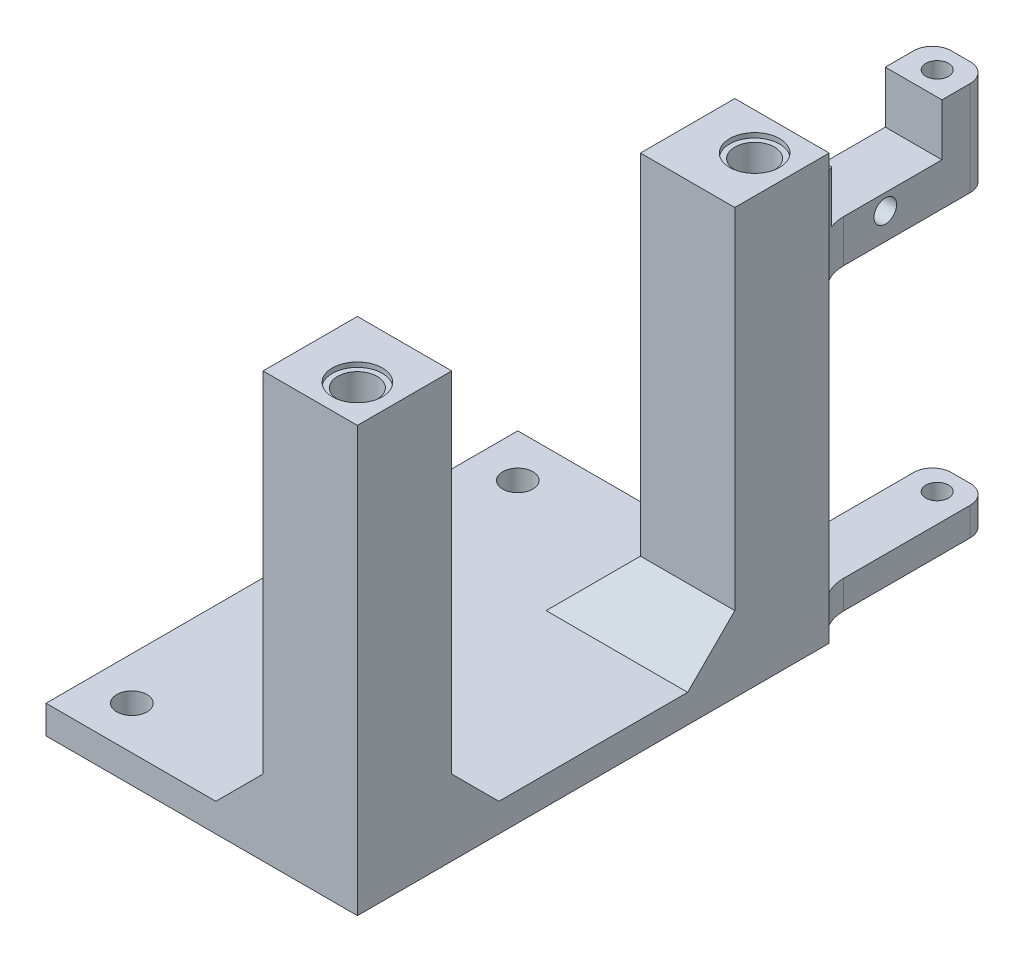
SolidWorks part; units mm, degrees
ref_plane "Front Plane" through (0, 0, 0) normal (0, 0, 1) x (1, 0, 0)
ref_plane "Top Plane" through (0, 0, 0) normal (0, 1, 0) x (1, 0, 0)
ref_plane "Right Plane" through (0, 0, 0) normal (1, 0, 0) x (0, 0, -1)
sketch "Sketch1" plane through (0, 0, 0) normal (0, 1, 0) x (1, 0, 0)
  line L1 (-6.5124, 9.686) -> (1.4876, 9.686)
  line L2 (-6.5124, 9.686) -> (-6.5124, -40.314)
  line L3 (-6.5124, -40.314) -> (1.4876, -40.314)
  line L4 (1.4876, 9.686) -> (1.4876, -40.314)
  line L5 (1.4876, 9.686) -> (26.4876, 9.686)
  line L6 (1.4876, 9.686) -> (1.4876, -40.314)
  line L7 (1.4876, -40.314) -> (26.4876, -40.314)
  line L8 (26.4876, 9.686) -> (26.4876, -40.314)
  circle A0 centre (-1.9624, -35.764) radius 1.6
  circle A1 centre (-1.9624, 5.136) radius 1.6
  dimension "D4" = 3.2
  dimension "D5" = 3.2
  dimension "D6" = 4.55
  dimension "D7" = 4.55
  dimension "D8" = 4.55
  dimension "D9" = 4.55
  dimension "D1" = 8
  dimension "D2" = 50
  dimension "D3" = 25
extrude "Boss-Extrude1" add sketch "Sketch1" along normal blind 3 contours A1 | A0 | L5 L8 L7 L3 L2 L1
sketch "Sketch2" plane through (0, 3, 0) normal (0, 1, 0) x (1, 0, 0)
  line L1 (26.4876, -40.314) -> (16.4876, -40.314)
  line L2 (26.4876, -40.314) -> (26.4876, -30.314)
  line L3 (26.4876, -30.314) -> (16.4876, -30.314)
  line L4 (16.4876, -40.314) -> (16.4876, -30.314)
  line L5 (26.4876, 9.686) -> (16.4876, 9.686)
  line L6 (26.4876, 9.686) -> (26.4876, -0.314)
  line L7 (26.4876, -0.314) -> (16.4876, -0.314)
  line L8 (16.4876, 9.686) -> (16.4876, -0.314)
  dimension "D1" = 10
  dimension "D2" = 10
  dimension "D3" = 10
  dimension "D4" = 10
extrude "Boss-Extrude2" add sketch "Sketch2" along normal blind 42
chamfer "Chamfer1" distance 5 angle 45 4 edges at (16.4876, 3, -4.686) (21.4876, 3, 0.314) (16.4876, 3, 35.314) (21.4876, 3, 30.314)
ref_plane "Plane1" through (0, 45, 0) normal (0, 1, 0) x (1, 0, 0)
sketch "Sketch3" plane through (0, 45, 0) normal (0, 1, 0) x (1, 0, 0)
  line L0 (26.4876, -40.314) -> (26.4876, -30.314) construction
  line L1 (16.4876, -40.314) -> (26.4876, -40.314) construction
  line L2 (26.4876, -0.314) -> (26.4876, 9.686) construction
  line L3 (26.4876, 9.686) -> (16.4876, 9.686) construction
  circle A0 centre (22.5376, -36.364) radius 2.1
  circle A1 centre (22.5376, 5.736) radius 2.1
  dimension "D1" = 4.2
  dimension "D3" = 3.95
  dimension "D4" = 4.2
  dimension "D6" = 3.95
  dimension "D2" = 3.95
  dimension "D5" = 3.95
extrude "Cut-Extrude1" cut sketch "Sketch3" against normal blind 52
sketch "Sketch4" plane through (0, 45, 0) normal (0, 1, 0) x (1, 0, 0)
  circle A0 centre (22.5376, -36.364) radius 2.65
  circle A1 centre (22.5376, 5.736) radius 2.65
  dimension "D1" = 5.3
  dimension "D2" = 5.3
extrude "Cut-Extrude2" cut sketch "Sketch4" against normal blind 0.5
ref_plane "Plane2" through (0, 22.5, 0) normal (0, -1, 0) x (-1, 0, 0)
mirror "Mirror1" about plane through (0, 22.5, 0) normal (0, -1, 0) of "Cut-Extrude2"
sketch "Sketch5" plane through (0, 0, -9.686) normal (0, 0, -1) x (-1, 0, 0)
  line L0 (-22.4876, 36.5) -> (-17.9876, 36.5) construction
  line L1 (-18.2876, 36.2) -> (-24.2876, 36.2)
  line L2 (-18.2876, 36.2) -> (-18.2876, 31.6868)
  line L3 (-18.2876, 31.6868) -> (-24.2876, 31.6868)
  line L4 (-24.2876, 36.2) -> (-24.2876, 31.6868)
  line L5 (-17.9876, 32.25) -> (-17.9876, 37) construction
  dimension "D1" = 0.3
  dimension "D2" = 0.3
  dimension "D3" = 6
extrude "Boss-Extrude3" add sketch "Sketch5" along normal up to surface (14.15 mm away)
sketch "Sketch6" plane through (24.2876, 0, 0) normal (1, 0, 0) x (0, 0, -1)
  circle A0 centre (17.836, 34.5) radius 1.2
  dimension "D1" = 2.4
extrude "Cut-Extrude3" cut sketch "Sketch6" against normal up to surface (6 mm away) up to face at (18.2876, 33.9434, -16.761)
sketch "Sketch7" plane through (0, 0, -23.836) normal (0, 0, -1) x (-1, 0, 0)
  line L1 (-24.2876, 31.6868) -> (-18.2876, 31.6868)
  line L2 (-24.2876, 31.6868) -> (-24.2876, 41.7057)
  line L3 (-24.2876, 41.7057) -> (-18.2876, 41.7057)
  line L4 (-18.2876, 31.6868) -> (-18.2876, 41.7057)
extrude "Boss-Extrude4" add sketch "Sketch7" along normal blind 5
sketch "Sketch8" plane through (0, 0, -9.686) normal (0, 0, -1) x (-1, 0, 0)
  line L0 (-18.2876, 41.7057) -> (-24.2876, 41.7057) construction
  line L1 (-24.2876, 36.2) -> (-18.2687, 36.2)
  line L2 (-24.2876, 36.2) -> (-24.2876, 41.7057)
  line L3 (-24.2876, 41.7057) -> (-18.2687, 41.7057)
  line L4 (-18.2687, 36.2) -> (-18.2687, 41.7057)
extrude "Boss-Extrude5" add sketch "Sketch8" along normal up to surface (2.15 mm away)
sketch "Sketch9" plane through (0, 0, -9.686) normal (0, 0, -1) x (-1, 0, 0)
  line L0 (6.5124, 0) -> (-26.4876, 0) construction
  line L1 (-24.2876, 0) -> (-18.2876, 0)
  line L2 (-24.2876, 0) -> (-24.2876, 3)
  line L3 (-24.2876, 3) -> (-18.2876, 3)
  line L4 (-18.2876, 0) -> (-18.2876, 3)
  line L5 (6.5124, 3) -> (-11.4876, 3) construction
  line L6 (-24.2876, 41.7057) -> (-24.2876, 31.6868) construction
  line L7 (-18.2876, 31.6868) -> (-18.2876, 41.7057) construction
extrude "Boss-Extrude6" add sketch "Sketch9" along normal up to surface (19.15 mm away) up to face at (21.2876, 36.6962, -28.836)
sketch "Sketch10" plane through (0, 41.7057, 0) normal (0, 1, 0) x (1, 0, 0)
  line L0 (18.2876, 23.836) -> (24.2876, 28.836) construction
  line L1 (18.2876, 28.836) -> (24.2876, 23.836) construction
  circle A0 centre (21.2876, 26.336) radius 1.2
  dimension "D1" = 2.4
extrude "Cut-Extrude4" cut sketch "Sketch10" against normal through all
fillet "Fillet3" radius 2 4 edges at (18.2876, 1.5, -28.836) (24.2876, 1.5, -28.836) (18.2876, 36.6962, -28.836) (24.2876, 36.6962, -28.836)
fillet "Fillet4" radius 4.25 1 edges at (24.2876, 1.5, -9.686)
fillet "Fillet5" radius 4.25 1 edges at (18.2876, 1.5, -9.686)
fillet "Fillet6" radius 4.25 1 edges at (24.2876, 36.6962, -9.686)
fillet "Fillet7" radius 4.25 1 edges at (18.2876, 33.9434, -9.686)
fillet "Fillet8" radius 1 1 edges at (20.2626, 3, -9.686)
fillet "Fillet9" radius 1 1 edges at (21.4876, 31.6868, -9.686)
sketch "Sketch11" plane through (0, 0, 40.314) normal (0, 0, 1) x (1, 0, 0)
  line L0 (16.4876, 45) -> (26.4876, 45) construction
  line L1 (18.4876, 45) -> (24.4876, 45)
  line L2 (18.4876, 45) -> (18.4876, 42)
  line L3 (18.4876, 42) -> (24.4876, 42)
  line L4 (24.4876, 45) -> (24.4876, 42)
  line L5 (-6.5124, 0) -> (26.4876, 0) construction
  line L6 (18.4876, 0) -> (24.4876, 0)
  line L7 (18.4876, 0) -> (18.4876, 3)
  line L8 (18.4876, 3) -> (24.4876, 3)
  line L9 (24.4876, 0) -> (24.4876, 3)
  line L10 (21.4876, 8) -> (21.4876, 0) construction
  line L11 (21.4876, 8) -> (21.4876, 45) construction
  line L13 (-6.5124, 3) -> (11.4876, 3) construction
  line L14 (16.4876, 8) -> (26.4876, 8) construction
  line L15 (26.4876, 8) -> (39.3241, 4.4212) construction
  line L16 (39.3241, 4.4212) -> (39.5028, 4.4212) construction
  dimension "D1" = 3
  dimension "D2" = 3
  dimension "D3" = 3
  dimension "D4" = 3
  dimension "D5" = 3
